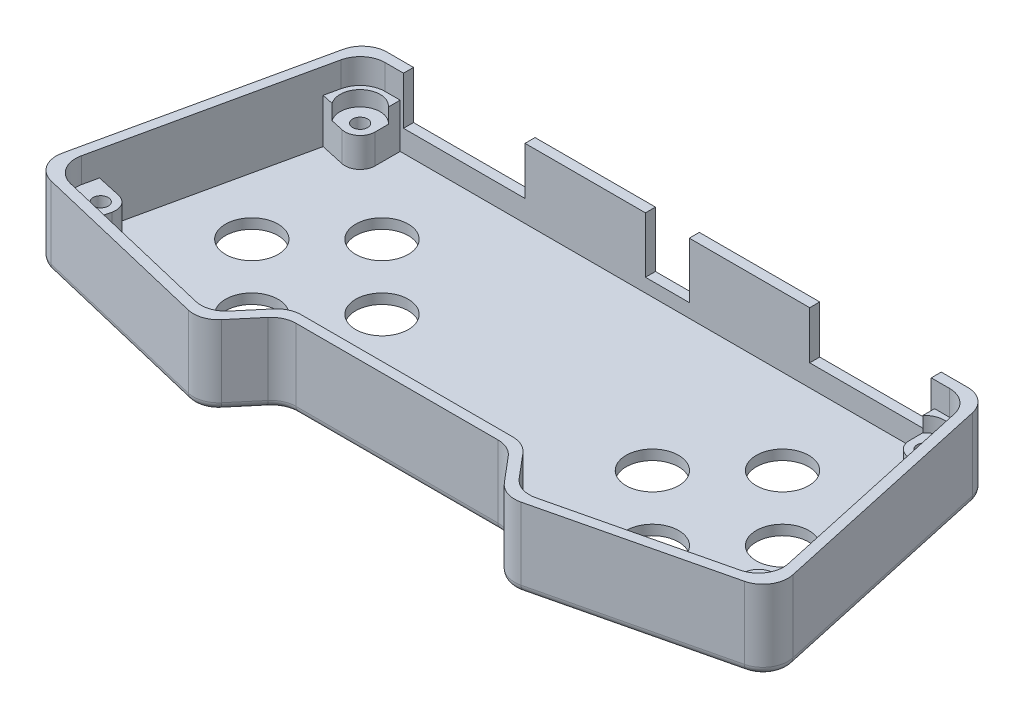
SolidWorks part; units mm, degrees
ref_plane "Front Plane" through (0, 0, 0) normal (0, 0, 1) x (1, 0, 0)
ref_plane "Top Plane" through (0, 0, 0) normal (0, 1, 0) x (1, 0, 0)
ref_plane "Right Plane" through (0, 0, 0) normal (1, 0, 0) x (0, 0, -1)
sketch "Sketch10" plane through (0, 0, 0) normal (0, 1, 0) x (1, 0, 0)
  line L0 (62, 32) -> (-62, 32)
  line L1 (-62, 32) -> (-74, -22.6992)
  line L2 (-74, -22.6992) -> (-30.236, -33.1736)
  line L3 (-30.236, -33.1736) -> (-22.5, -24)
  line L4 (-22.5, -24) -> (22.5, -24)
  line L5 (22.5, -24) -> (30.236, -33.1736)
  line L6 (30.236, -33.1736) -> (74, -22.6992)
  line L7 (74, -22.6992) -> (62, 32)
  line L8 (40, 13) -> (40, -13) construction
  line L9 (27, 0) -> (53, 0) construction
  line L10 (-40, 13) -> (-40, -13) construction
  line L11 (-53, 0) -> (-27, 0) construction
  line L12 (-27, 0) -> (27, 0) construction
  line L13 (0, 0) -> (0, 32) construction
  line L14 (0, 0) -> (0, -24) construction
  line L15 (74, -22.6992) -> (22.5, -24) construction
  line L16 (-22.5, -24) -> (-74, -22.6992) construction
  circle A0 centre (40, 13) radius 5.25
  circle A1 centre (27, 0) radius 5.25
  circle A2 centre (40, -13) radius 5.25
  circle A3 centre (53, 0) radius 5.25
  circle A4 centre (-40, 13) radius 5.25
  circle A5 centre (-53, 0) radius 5.25
  circle A6 centre (-40, -13) radius 5.25
  circle A7 centre (-27, 0) radius 5.25
  point P16 (40, 0)
  point P17 (-40, 0)
  point P27 (-28.9781, -30.2818)
  dimension "D1" = 10.5
  dimension "D2" = 26
  dimension "D3" = 56
  dimension "D4" = 124
  dimension "D5" = 80
  dimension "D6" = 148
  dimension "D7" = 56
  dimension "D8" = 45
  dimension "D9" = 32
  dimension "D10" = 45
  dimension "D11" = 12
extrude "Boss-Extrude5" add sketch "Sketch10" along normal blind 2 separate body
sketch "Sketch11" plane through (0, 2, 0) normal (0, 1, 0) x (1, 0, 0)
  line L0 (-74, -22.6992) -> (-62, 32)
  line L1 (-62, 32) -> (62, 32)
  line L2 (62, 32) -> (74, -22.6992)
  line L3 (74, -22.6992) -> (30.236, -33.1736)
  line L4 (30.236, -33.1736) -> (22.5, -24)
  line L5 (22.5, -24) -> (-22.5, -24)
  line L6 (-22.5, -24) -> (-30.236, -33.1736)
  line L7 (-30.236, -33.1736) -> (-74, -22.6992)
  line L8 (-30.9699, -30.9414) -> (-71.6259, -21.2109)
  line L9 (-71.6259, -21.2109) -> (-60.3912, 30)
  line L10 (-60.3912, 30) -> (60.3912, 30)
  line L11 (60.3912, 30) -> (71.6259, -21.2109)
  line L12 (71.6259, -21.2109) -> (30.9699, -30.9414)
  line L13 (30.9699, -30.9414) -> (23.4296, -22)
  line L14 (23.4296, -22) -> (-23.4296, -22)
  line L15 (-23.4296, -22) -> (-30.9699, -30.9414)
  dimension "D1" = 2
extrude "Boss-Extrude7" add sketch "Sketch11" along direction (0, -1, 0) on the side of the normal offset from surface (13.875 mm away) 15.875 up to face at (-40, 0, 18.25)
fillet "Fillet4" radius 5 16 edges at (62, 7.9375, -32) (74, 7.9375, 22.6992) (30.236, 7.9375, 33.1736) (22.5, 7.9375, 24) (-22.5, 7.9375, 24) (-30.236, 7.9375, 33.1736) (-62, 7.9375, -32) (-74, 7.9375, 22.6992) (71.6259, 8.9375, 21.2109) (60.3912, 8.9375, -30) (30.9699, 8.9375, 30.9414) (23.4296, 8.9375, 22) (-23.4296, 8.9375, 22) (-30.9699, 8.9375, 30.9414) (-71.6259, 8.9375, 21.2109) (-60.3912, 8.9375, -30)
fillet "Fillet5" radius 1.5 16 edges at (30.509, 0, 32.3431) (26.1233, 0, 28.2966) (22.2835, 0, 24.4659) (0, 0, 24) (-22.2835, 0, 24.4659) (-26.1233, 0, 28.2966) (-30.509, 0, 32.3431) (-51.2316, 0, 28.1485) (-72.3012, 0, 21.6342) (-67.9053, 0, -5.0822) (-61.1119, 0, -30.896) (0, 0, -32) (61.1119, 0, -30.896) (67.9053, 0, -5.0822) (72.3012, 0, 21.6342) (51.2316, 0, 28.1485)
sketch "Sketch12" plane through (0, 2, 0) normal (0, 1, 0) x (1, 0, 0)
  line L0 (-61.8959, 23.1411) -> (-57.0121, 22.0697)
  line L1 (-61.2531, 26.0714) -> (-70.5746, -16.4188) construction
  line L2 (-53.3692, 25) -> (-53.3692, 30)
  line L3 (56.3692, 30) -> (-56.3692, 30) construction
  line L4 (-53.3692, 30) -> (-56.3692, 30)
  line L5 (-61.2531, 26.0714) -> (-61.8959, 23.1411)
  line L6 (-70.5746, -16.4188) -> (-69.9318, -13.4885)
  line L7 (-69.9318, -13.4885) -> (-65.0479, -14.5599)
  line L8 (-62.7732, -18.1885) -> (-63.937, -23.0512)
  line L9 (-66.8546, -22.3529) -> (-33.9684, -30.2238) construction
  line L10 (-63.937, -23.0512) -> (-66.8546, -22.3529)
  line L11 (0, 0) -> (0, 17.9434) construction
  line L12 (63.937, -23.0512) -> (66.8546, -22.3529)
  line L13 (62.7732, -18.1885) -> (63.937, -23.0512)
  line L14 (69.9318, -13.4885) -> (65.0479, -14.5599)
  line L15 (70.5746, -16.4188) -> (69.9318, -13.4885)
  line L16 (61.2531, 26.0714) -> (61.8959, 23.1411)
  line L17 (53.3692, 30) -> (56.3692, 30)
  line L18 (53.3692, 25) -> (53.3692, 30)
  line L19 (61.8959, 23.1411) -> (57.0121, 22.0697)
  arc A0 (-57.0121, 22.0697) -> (-53.3692, 25) centre (-56.3692, 25) ccw
  arc A1 (-56.3692, 30) -> (-61.2531, 26.0714) centre (-56.3692, 25) ccw
  arc A2 (-65.0479, -14.5599) -> (-62.7732, -18.1885) centre (-65.6908, -17.4902) cw
  arc A3 (-66.8546, -22.3529) -> (-70.5746, -16.4188) centre (-65.6908, -17.4902) cw
  circle A4 centre (-56.3692, 25) radius 1.5
  circle A5 centre (-65.6908, -17.4902) radius 1.5
  circle A6 centre (65.6908, -17.4902) radius 1.5
  circle A7 centre (56.3692, 25) radius 1.5
  arc A8 (66.8546, -22.3529) -> (70.5746, -16.4188) centre (65.6908, -17.4902) ccw
  arc A9 (65.0479, -14.5599) -> (62.7732, -18.1885) centre (65.6908, -17.4902) ccw
  arc A10 (56.3692, 30) -> (61.2531, 26.0714) centre (56.3692, 25) cw
  arc A11 (57.0121, 22.0697) -> (53.3692, 25) centre (56.3692, 25) cw
  dimension "D1" = 3
  dimension "D2" = 1.5
extrude "Boss-Extrude8" add sketch "Sketch12" along normal offset from surface (8.875 mm away) 5 up to face at (0, 15.875, 10.9337)
sketch "Sketch13" plane through (0, 10.875, 0) normal (0, 1, 0) x (1, 0, 0)
  circle A0 centre (-56.3692, 25) radius 4
  circle A1 centre (56.3692, 25) radius 4
  dimension "D1" = 8
extrude "Cut-Extrude1" cut sketch "Sketch13" against normal blind 3
sketch "Sketch14" plane through (0, 0, -30) normal (0, 0, 1) x (1, 0, 0)
  line L0 (-56.3692, 15.875) -> (56.3692, 15.875) construction
  line L1 (-52.7009, 15.875) -> (-28.427, 15.875)
  line L2 (-52.7009, 15.875) -> (-52.7009, 6.3348)
  line L3 (-52.7009, 6.3348) -> (-28.427, 6.3348)
  line L4 (-28.427, 15.875) -> (-28.427, 6.3348)
  line L5 (0, 0) -> (0, 15.875) construction
  line L6 (28.427, 15.875) -> (28.427, 6.3348)
  line L7 (52.7009, 6.3348) -> (28.427, 6.3348)
  line L8 (52.7009, 15.875) -> (52.7009, 6.3348)
  line L9 (52.7009, 15.875) -> (28.427, 15.875)
  line L11 (-4.3796, 15.875) -> (4.3796, 15.875)
  line L12 (-4.3796, 15.875) -> (-4.3796, 4.7297)
  line L13 (-4.3796, 4.7297) -> (4.3796, 4.7297)
  line L14 (4.3796, 15.875) -> (4.3796, 4.7297)
extrude "Cut-Extrude2" cut sketch "Sketch14" against normal through all
